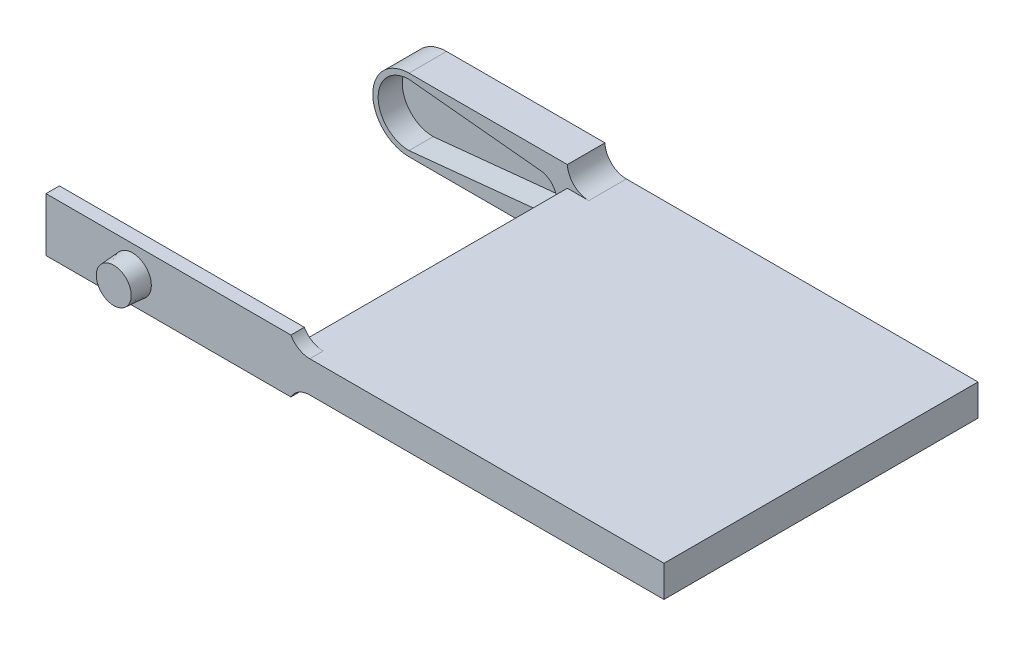
SolidWorks part; units mm, degrees
ref_plane "Front Plane" through (0, 0, 0) normal (0, 0, 1) x (1, 0, 0)
ref_plane "Top Plane" through (0, 0, 0) normal (0, 1, 0) x (1, 0, 0)
ref_plane "Right Plane" through (0, 0, 0) normal (1, 0, 0) x (0, 0, -1)
ref_plane "Ground Plane" through (0, 0, 29.25) normal (0, 0, -1) x (-1, 0, 0)
sketch "Sketch1" plane through (0, 0, 0) normal (0, 0, 1) x (1, 0, 0)
  line L0 (0, 3.375) -> (-13.75, 3.375) construction
  line L1 (0, 3.375) -> (0, 6.25) construction
  line L2 (-12.2651, 5.0167) -> (0, 6.25)
  line L3 (-13.75, 3.375) -> (-13.75, 1.1142) construction
  line L4 (-12.2651, 1.7333) -> (0, 0.5)
  line L5 (12.2651, 1.7333) -> (0, 0.5)
  line L6 (12.2651, 5.0167) -> (0, 6.25)
  line L7 (-2.875, 3.375) -> (-2.875, -5.5898) construction
  line L8 (-14.75, 0) -> (14.75, 0)
  line L9 (-14.75, 0) -> (-14.75, 6.75)
  line L10 (-14.75, 6.75) -> (14.75, 6.75)
  line L11 (-43.5503, 24.4221) -> (7.9447, 11.3967) construction
  line L12 (13.75, 3.375) -> (13.75, 0.9067) construction
  line L13 (14.75, 4.8371) -> (49.5, 4.8371)
  line L14 (14.5, 4.8371) -> (14.5, 1.9129) construction
  line L15 (14.75, 1.9129) -> (49.5, 1.9129)
  line L16 (49.5, 4.8371) -> (49.5, 1.9129)
  line L17 (-43.5503, 24.4221) -> (7.9447, 11.3967)
  line L18 (14.75, 6.75) -> (14.75, 0)
  line L19 (8.1899, 12.3661) -> (3.8863, -4.648) construction
  line L20 (8.1899, 12.3661) -> (3.8863, -4.648)
  line L21 (8.1899, 12.3661) -> (3.8863, -4.648)
  line L22 (8.1899, 12.3661) -> (3.8863, -4.648) construction
  line L23 (8.1899, 12.3661) -> (3.8863, -4.648)
  circle A0 centre (0, 3.375) radius 2.875 construction
  arc A1 (-12.2651, 5.0167) -> (-12.2651, 1.7333) centre (-12.1, 3.375) ccw
  arc A2 (12.2651, 5.0167) -> (12.2651, 1.7333) centre (12.1, 3.375) cw
  circle A3 centre (-12.1, 3.375) radius 0.2914
  circle A4 centre (-10.0632, 3.375) radius 0.2914
  circle A5 centre (-8.0264, 3.375) radius 0.2914
  circle A6 centre (8.0264, 3.375) radius 0.2914
  circle A7 centre (10.0632, 3.375) radius 0.2914
  circle A8 centre (12.1, 3.375) radius 0.2914
  arc A9 (0, 6.75) -> (0, 0) centre (0, 3.375) ccw
  arc A10 (0, 6.25) -> (0, 0.5) centre (0, 3.375) ccw
  point P2 (-14.75, 3.375)
  point P27 (0, 6.75)
  point P34 (14.5, 3.375)
  point P35 (49.5, 3.375)
  dimension "D1" = 5.75
  dimension "D9" = 1.65
  dimension "D3" = 2.9241
  dimension "D5" = 29.5
  dimension "D7" = 6.75
  dimension "D8" = 1.7333
  dimension "D11" = 27.5
  dimension "D6" = 13.75
  dimension "D2" = 3
extrude "Boss-Extrude10" add sketch "Sketch1" along normal blind 3.5 contours L4 A9 L8 L20 L5 | L6 A2 L5 L20 L8 L18 L10 | L10 A9 L2 L6 L20 | A10 L2 A9 L4 region at (3.1883, 6.3261, 0) region at (-1.314, 6.0546, 0) region at (2.2829, 0.3947, 0) region at (10.7597, 6.6319, 0)
extrude "Boss-Extrude15" add sketch "Sketch1<16>" along normal blind 1.25 contours A7 | A8 | L2 A0 L4 L5 L6 | A2 L6 A0 L5 A7 A6 A8 | A6 region at (1.6334, 3.4211, 0) region at (9.4045, 3.3032, 0) region at (10.0632, 3.375, 0) region at (12.1, 3.375, 0)
sketch "Sketch1<16>" plane through (0, 0, 0) normal (0, 0, 1) x (1, 0, 0) same geometry as "Sketch1"
extrude "Boss-Extrude17" add sketch "Sketch1<17>" along direction (0, 0, -1) on the side of the normal up to surface (29.25 mm away) contours L13 L18 L15 L16 region at (32.125, 3.375, 0) up to plane "Ground Plane"
sketch "Sketch1<17>" plane through (0, 0, 0) normal (0, 0, 1) x (1, 0, 0) same geometry as "Sketch1"
sketch "Sketch2" plane through (0, 0, 29.25) normal (0, 0, 1) x (1, 0, 0)
  line L0 (0, 2.75) -> (0, 3.375) construction
  line L1 (13.5, 5.875) -> (-8.0614, 5.875)
  line L3 (14.75, 0.875) -> (-8.0614, 0.875)
  line L4 (-8.0614, 5.875) -> (-8.0614, 0.875)
  line L6 (14.75, 4.8371) -> (14.75, 1.9129) construction
  line L7 (13.5, 5.875) -> (14.75, 5.875)
  line L8 (14.75, 5.875) -> (14.75, 0.875)
  circle A0 centre (0, 3.375) radius 1.75
  circle A3 centre (0, 3.375) radius 2.875 construction
  point P12 (14.5, 3.375)
  dimension "D1" = 3.5
  dimension "D2" = 5
extrude "Boss-Extrude18" add sketch "Sketch2" against normal blind 1.25 contours L1 L4 L3 L8 L7
extrude "Boss-Extrude19" add sketch "Sketch2<9>" along normal blind 1.75 draft 4 contours A0
sketch "Sketch2<9>" plane through (0, 0, 29.25) normal (0, 0, 1) x (1, 0, 0) same geometry as "Sketch2"
fillet "Fillet1" radius 2 4 edges at (14.75, 1.9129, 28.625) (14.75, 4.8371, 28.625)
fillet "Fillet2" [suppressed] radius 4
sketch "Sketch3" [suppressed] plane through (0, 0, 3.5) normal (0, 0, 1) x (1, 0, 0)
  line L0 (-0.1021, 0) -> (-0.1021, 6.75) construction
  line L1 (-2.9771, 6.75) -> (-2.9771, 0) construction
  line L3 (-10.75, 6.75) -> (14.75, 6.75) construction
  line L4 (-14.7009, 3.375) -> (-0.1021, 3.375) construction
  line L5 (2.7729, 6.75) -> (2.7729, 0) construction
  line L6 (2.7729, 6.75) -> (2.7729, 5.625)
  line L7 (-2.9771, 5.625) -> (2.7729, 5.625)
  line L8 (-2.9771, 0) -> (2.7729, 0)
  line L9 (-2.9771, 0) -> (-2.9771, 1.125)
  line L10 (-2.9771, 1.125) -> (2.7729, 1.125)
  line L11 (2.7729, 0) -> (2.7729, 1.125)
  line L12 (-2.9771, 6.75) -> (2.7729, 6.75)
  line L13 (-2.9771, 6.75) -> (-2.9771, 5.625)
  line L19 (-10.75, 0) -> (14.75, 0) construction
  circle A0 centre (-0.1021, 3.375) radius 2.875 construction
  circle A1 centre (-0.1021, 3.375) radius 2.875 construction
  circle A2 centre (-0.1021, 3.375) radius 2.25 construction
  circle A3 centre (-0.1021, 3.375) radius 2.25 construction
extrude "Cut-Extrude1" [suppressed] cut sketch "Sketch3" against normal up to surface (2.25 mm away)
equation "\"D5@Sketch1\"=\"D6@Sketch1\"*2+2"
